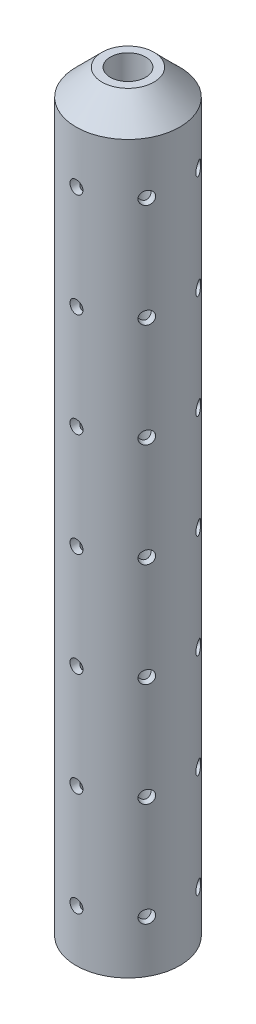
SolidWorks part; units mm, degrees
ref_plane "Front Plane" through (0, 0, 0) normal (0, 0, 1) x (1, 0, 0)
ref_plane "Top Plane" through (0, 0, 0) normal (0, 1, 0) x (1, 0, 0)
ref_plane "Right Plane" through (0, 0, 0) normal (1, 0, 0) x (0, 0, -1)
sketch "Sketch1" plane through (0, 0, 0) normal (0, 1, 0) x (1, 0, 0)
  line L1 (3.6955, 0) -> (1.8478, 3.2004)
  line L2 (1.8478, 3.2004) -> (-1.8478, 3.2004)
  line L3 (-1.8478, 3.2004) -> (-3.6955, 0)
  line L4 (-3.6955, 0) -> (-1.8478, -3.2004)
  line L5 (-1.8478, -3.2004) -> (1.8478, -3.2004)
  line L6 (1.8478, -3.2004) -> (3.6955, 0)
  circle A0 centre (0, 0) radius 3.2004 construction
  circle A1 centre (0, 0) radius 6.35
  dimension "D1" = 6.4008
  dimension "D2" = 12.7
extrude "Boss-Extrude1" add sketch "Sketch1" along normal blind 88.9
sketch "Sketch2" plane through (0, 88.9, 0) normal (0, 1, 0) x (1, 0, 0)
  circle A1 centre (0, 0) radius 2.159
  circle A2 centre (0, 0) radius 6.35
  circle A3 centre (0, 0) radius 6.35
  dimension "D2" = 4.318
  dimension "D1" = 0
extrude "Boss-Extrude2" add sketch "Sketch2" along normal blind 3.175
chamfer "Chamfer1" distance 3.175 distance2 3.175 1 edges at (0, 92.075, 6.35)
sketch "Sketch4" plane through (0, 0, 0) normal (0, -1, 0) x (1, 0, 0)
  circle A0 centre (0, 4.7625) radius 0.7938
  point P2 (0, 0)
  dimension "D2" = 1.5875
  dimension "D1" = 4.7625
extrude "Cut-Extrude1" cut sketch "Sketch4" against normal blind 88.9
ref_plane "Plane1" through (0, 0, 12.7) normal (0, 0, 1) x (1, 0, 0)
sketch "Sketch3" plane through (0, 0, 12.7) normal (0, 0, 1) x (1, 0, 0)
  line L0 (-6.35, 88.9) -> (6.35, 88.9) construction
  line L1 (0, 82.55) -> (0, 69.85) construction
  circle A0 centre (0, 82.55) radius 0.7937
  circle A1 centre (0, 69.85) radius 0.7937
  circle A2 centre (0, 57.15) radius 0.7937
  circle A3 centre (0, 44.45) radius 0.7937
  circle A4 centre (0, 31.75) radius 0.7937
  circle A5 centre (0, 19.05) radius 0.7937
  circle A6 centre (0, 6.35) radius 0.7938
  point P4 (0, 0)
  dimension "D2" = 1.5875
  dimension "D1" = 6.35
  dimension "D4" = 12.7
  dimension "D3" = 7
extrude "Cut-Extrude2" cut sketch "Sketch3" against normal up to surface (7.9375 mm away) up to face at (0, 88.9, 3.9688)
pattern_circular "CirPattern1" count 6 over 360 about axis through (0, 92.075, 0) along (0, 1, 0) of "Cut-Extrude1", "Cut-Extrude2"
